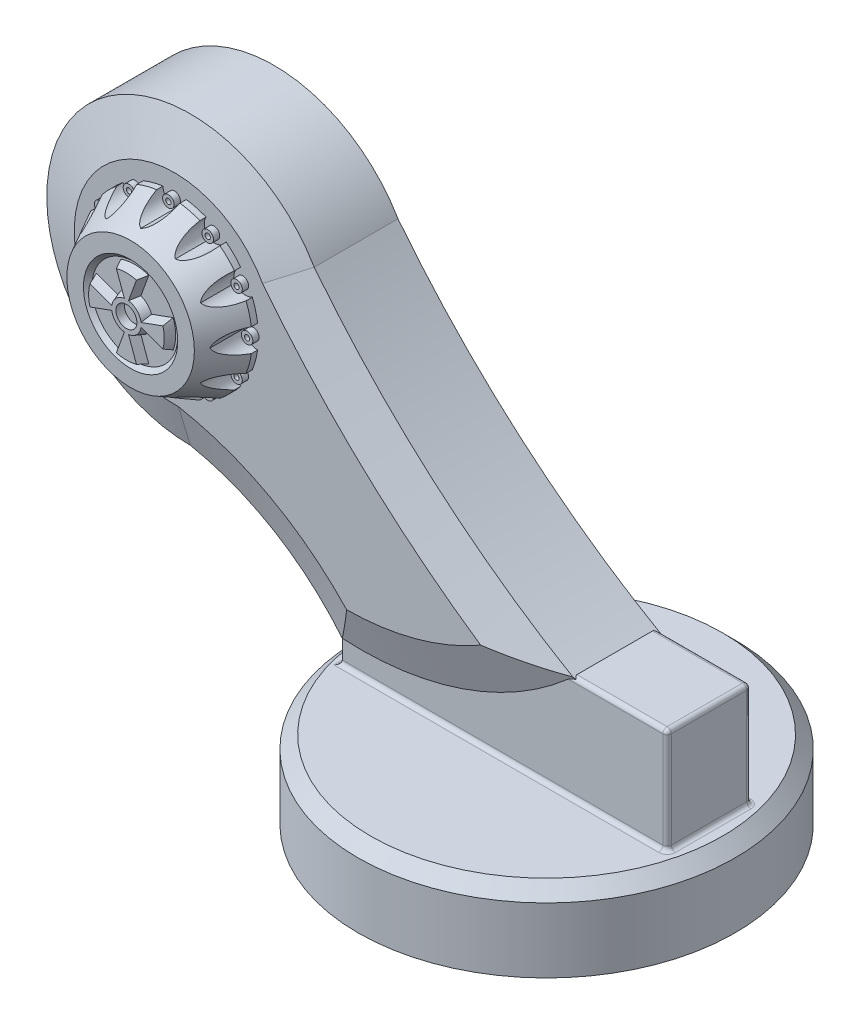
SolidWorks part; units mm, degrees
ref_plane "Front Plane" through (0, 0, 0) normal (0, 0, 1) x (1, 0, 0)
ref_plane "Top Plane" through (0, 0, 0) normal (0, 1, 0) x (1, 0, 0)
ref_plane "Right Plane" through (0, 0, 0) normal (1, 0, 0) x (0, 0, -1)
sketch "Sketch1" plane through (0, 0, 0) normal (0, 1, 0) x (1, 0, 0)
  circle A0 centre (0, 0) radius 90
  dimension "D1" = 180
extrude "Boss-Extrude1" add sketch "Sketch1" along normal blind 37
chamfer "Chamfer1" distance 6 angle 45 1 edges at (0, 37, 90)
sketch "Sketch2" plane through (0, 37, 0) normal (0, 1, 0) x (1, 0, 0)
  line L1 (-77.5, 20) -> (77.5, 20)
  line L2 (-77.5, 20) -> (-77.5, -20)
  line L3 (-77.5, -20) -> (77.5, -20)
  line L4 (77.5, 20) -> (77.5, -20)
  line L5 (-77.5, 20) -> (77.5, -20) construction
  line L6 (-77.5, -20) -> (77.5, 20) construction
  point P0 (0, 0)
  dimension "D1" = 155
  dimension "D2" = 40
extrude "Boss-Extrude2" add sketch "Sketch2" along normal blind 50
sketch "Sketch3" plane through (0, 0, 20) normal (0, 0, 1) x (1, 0, 0)
  line L0 (-77.5, 87) -> (32.5, 87)
  line L1 (-77.5, 87) -> (77.5, 87) construction
  line L2 (-77.5, 87) -> (-77.5, 48)
  line L3 (-77.5, 87) -> (-77.5, 37) construction
  arc A0 (32.5, 87) -> (-77.5, 48) centre (-68.6761, 197.7402) cw
  dimension "D3" = 150
  dimension "D1" = 110
  dimension "D2" = 39
extrude "Cut-Extrude3" cut sketch "Sketch3" against normal through all
sketch "Sketch4" plane through (0, 0, 0) normal (0, 0, 1) x (1, 0, 0)
  line L0 (0, 0) -> (-150, 0)
  line L1 (-150, 0) -> (-150, 160)
  circle A0 centre (-150, 160) radius 68.5
  arc A1 (-150, 91.5) -> (-77.5, 48) centre (-174.2724, -31.1207) cw
  arc A2 (-90.9032, 194.6384) -> (32.5, 87) centre (254.9721, 466.6132) ccw
  arc A3 (32.5, 87) -> (-77.5, 48) centre (-68.6761, 197.7402) cw
  dimension "D3" = 137
  dimension "D4" = 440
  dimension "D5" = 125
  dimension "D1" = 150
  dimension "D2" = 160
  dimension "D6" = 254.9721
extrude "Boss-Extrude3" add sketch "Sketch4" along normal mid plane 40 contours A3 A2 A0 A1 | A0 region at (-102.9332, 112.9332, 0) region at (-53.6257, 97.99, 0)
sketch "Sketch5" plane through (0, 0, 20) normal (0, 0, 1) x (1, 0, 0)
  circle A0 centre (-150, 160) radius 68.5 construction
  circle A1 centre (-150, 160) radius 68.5
  arc A2 (-90.9032, 194.6384) -> (32.5, 87) centre (254.9721, 466.6132) ccw construction
  arc A3 (-90.9032, 194.6384) -> (32.5, 87) centre (254.9721, 466.6132) ccw
  arc A4 (-77.5, 48) -> (-150, 91.5) centre (-174.2724, -31.1207) ccw construction
  arc A5 (-77.5, 48) -> (-150, 91.5) centre (-174.2724, -31.1207) ccw
  arc A6 (-77.5, 48) -> (32.5, 87) centre (-68.6761, 197.7402) ccw construction
  arc A7 (-77.5, 48) -> (32.5, 87) centre (-68.6761, 197.7402) ccw
  arc M4 (32.5, 87) -> (-90.9032, 194.6384) centre (254.9721, 466.6132) cw
  arc M5 (-90.9032, 194.6384) -> (-150, 91.5) centre (-150, 160) ccw
  arc M6 (-150, 91.5) -> (-77.5, 48) centre (-174.2724, -31.1207) cw
extrude "Boss-Extrude4" add sketch "Sketch5" along normal blind 7.5 draft 70 contours A7 A1 M6 M4 | A1 M5 region at (-150, 160, 20) region at (-53.6257, 97.99, 20)
sketch "Sketch6" plane through (0, 0, 27.5) normal (0, 0, 1) x (1, 0, 0)
  circle A0 centre (-150, 160) radius 40
  dimension "D1" = 80
extrude "Boss-Extrude5" add sketch "Sketch6" along normal blind 3
sketch "Sketch7" plane through (0, 0, 30.5) normal (0, 0, 1) x (1, 0, 0)
  circle A0 centre (-150, 160) radius 40 construction
  circle A1 centre (-150, 160) radius 40
extrude "Boss-Extrude6" add sketch "Sketch7" along normal blind 18 draft 28
sketch "Sketch10" plane through (0, 0, 48.5) normal (0, 0, 1) x (1, 0, 0)
  line L0 (-150, 160) -> (-150, 193) construction
  arc A0 (-150, 193) -> (-144.4439, 199.6122) centre (-151.4399, 199.8503) ccw
  arc A2 (-150, 193) -> (-155.5561, 199.6122) centre (-148.5601, 199.8503) cw
  circle A3 centre (-150, 160) radius 40 construction
  arc A4 (-155.5561, 199.6122) -> (-144.4439, 199.6122) centre (-150, 160) cw
  point P15 (-150, 199.7815)
  dimension "7" = 7
extrude "Cut-Extrude4" cut sketch "Sketch10" against normal up to surface (21 mm away) up to face at (-110, 160, 27.5)
sketch "Sketch11" plane through (0, 0, 27.5) normal (0, 0, 1) x (1, 0, 0)
  circle A1 centre (-150, 197.5791) radius 2.75
  circle A2 centre (-150, 197.5791) radius 1.25
  dimension "D1" = 5.5
  dimension "D2" = 2.5
extrude "Boss-Extrude7" add sketch "Sketch11" along normal blind 3
pattern_circular "CirPattern1" count 12 over 360 about axis through (-150, 160, 48.5) along (0, 0, 1) of "Boss-Extrude7", "Cut-Extrude4"
sketch "Sketch12" plane through (0, 0, 48.5) normal (0, 0, 1) x (1, 0, 0)
  circle A0 centre (-150, 160) radius 22.5
  dimension "D1" = 45
extrude "Cut-Extrude5" cut sketch "Sketch12" against normal blind 2 draft 45
sketch "Sketch13" plane through (0, 0, 46.5) normal (0, 0, 1) x (1, 0, 0)
  line L0 (-142.0126, 162.9072) -> (-131.676, 166.6694)
  line L1 (-152.9072, 167.9874) -> (-156.6694, 178.324)
  line L2 (-147.0928, 167.9874) -> (-143.3306, 178.324)
  line L3 (-142.0126, 157.0928) -> (-131.676, 153.3306)
  line L4 (-147.0928, 152.0126) -> (-143.3306, 141.676)
  line L5 (-152.9072, 152.0126) -> (-156.6694, 141.676)
  line L6 (-157.9874, 157.0928) -> (-168.324, 153.3306)
  line L7 (-157.9874, 162.9072) -> (-168.324, 166.6694)
  circle A0 centre (-150, 160) radius 19.5
  arc A1 (-157.9874, 157.0928) -> (-152.9072, 152.0126) centre (-150, 160) ccw
  arc A2 (-152.9072, 167.9874) -> (-157.9874, 162.9072) centre (-150, 160) ccw
  arc A3 (-142.0126, 162.9072) -> (-147.0928, 167.9874) centre (-150, 160) ccw
  arc A4 (-147.0928, 152.0126) -> (-142.0126, 157.0928) centre (-150, 160) ccw
  point P23 (-150, 160)
  dimension "D1" = 39
  dimension "D2" = 17
  dimension "D3" = 4
extrude "Boss-Extrude8" add sketch "Sketch13" along normal blind 4 draft 20 contours L4 A4 L3 A0 L0 A3 L2 L1 A2 L7 L6 A1 L5 region at (-150, 160, 46.5)
sketch "Sketch14" plane through (0, 0, 50.5) normal (0, 0, 1) x (1, 0, 0)
  circle A0 centre (-150, 160) radius 5
  dimension "D1" = 10
extrude "Cut-Extrude6" cut sketch "Sketch14" against normal up to surface (4 mm away) up to face at (-129.5, 160, 46.5)
fillet "Fillet3" radius 2 6 edges at (77.5, 87, 0) (0, 37, -20) (0, 37, 20) (77.5, 37, 0) (77.5, 62, 20) (77.5, 62, -20)
fillet "Fillet4" radius 2 1 edges at (-77.5, 37, 0)
fillet "Fillet10" radius 2 4 edges at (76.9142, 86.4142, -19.4142) (76.9142, 86.4142, 19.4142) (54, 87, -20) (54, 87, 20)
sketch "Sketch15" plane through (0, 0, -20) normal (0, 0, -1) x (-1, 0, 0)
  circle A0 centre (150, 160) radius 15
  dimension "D1" = 30
extrude "Cut-Extrude7" cut sketch "Sketch15" against normal blind 20
sketch "Sketch16" plane through (0, 0, 0) normal (0, -1, 0) x (1, 0, 0)
  circle A0 centre (0, 0) radius 15
  dimension "D1" = 30
extrude "Cut-Extrude8" cut sketch "Sketch16" against normal blind 20
